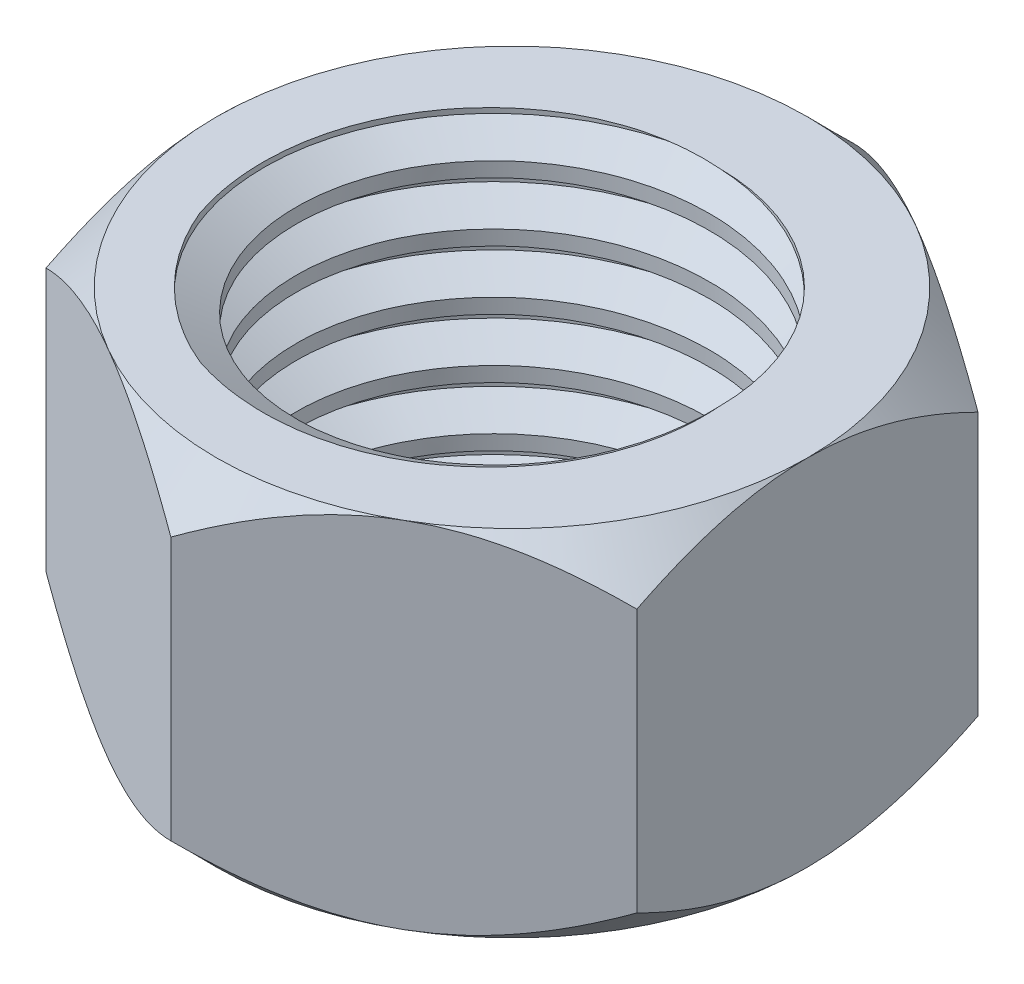
SolidWorks part; units mm, degrees
ref_plane "Front Plane" through (0, 0, 0) normal (0, 0, 1) x (1, 0, 0)
ref_plane "Top Plane" through (0, 0, 0) normal (0, 1, 0) x (1, 0, 0)
ref_plane "Right Plane" through (0, 0, 0) normal (1, 0, 0) x (0, 0, -1)
sketch "Sketch1" plane through (0, 0, 0) normal (0, 1, 0) x (1, 0, 0)
  line L1 (0, 5.7735) -> (-5, 2.8868)
  line L2 (-5, 2.8868) -> (-5, -2.8868)
  line L3 (-5, -2.8868) -> (0, -5.7735)
  line L4 (0, -5.7735) -> (5, -2.8868)
  line L5 (5, -2.8868) -> (5, 2.8868)
  line L6 (5, 2.8868) -> (0, 5.7735)
  circle A0 centre (0, 0) radius 5 construction
  dimension "D2" = 10
extrude "Boss-Extrude1" add sketch "Sketch1" along normal mid plane 6
sketch "Sketch9" plane through (0, 3, 0) normal (0, 1, 0) x (1, 0, 0)
  circle A0 centre (0, 0) radius 5
  dimension "D1" = 10
extrude "Cut-Extrude3" cut sketch "Sketch9" against normal through all draft 45 flip side to cut
mirror "Mirror1" about plane through (0, 0, 0) normal (0, 1, 0) of "Cut-Extrude3"
sketch "Sketch10" plane through (0, 3, 0) normal (0, 1, 0) x (1, 0, 0)
  circle A0 centre (0, 0) radius 3.5
  dimension "D1" = 7
extrude "Cut-Extrude4" cut sketch "Sketch10" against normal through all
thread "Thread1" pitch 1 method cut profile "Thread Profile2" start angle 0, offset 1, length 7, pitch 1, diameter 7
ref_plane "Plane2" through (3.5, -4, 0) normal (0, 0, 1) x (1, 0, 0)
sketch "Thread Profile2" plane through (3.5, -4, 0) normal (0, 0, 1) x (1, 0, 0)
  line L0 (0, 0) -> (0, 1) construction
  line L1 (0, 0) -> (0.5413, 0.3125)
  line L2 (0.5413, 0.3125) -> (0.5413, 0.4375)
  line L3 (0.5413, 0.4375) -> (0, 0.75)
  line L4 (0.5413, 0.375) -> (0, 0.375) construction
  line L11 (0, 0) -> (0, 0.75)
  point P2 (0, 0)
  dimension "Pitch" = 1
  dimension "Profile_Angle" = 60
  dimension "Profile_Land" = 0.125
  dimension "Profile_Height" = 0.5413
